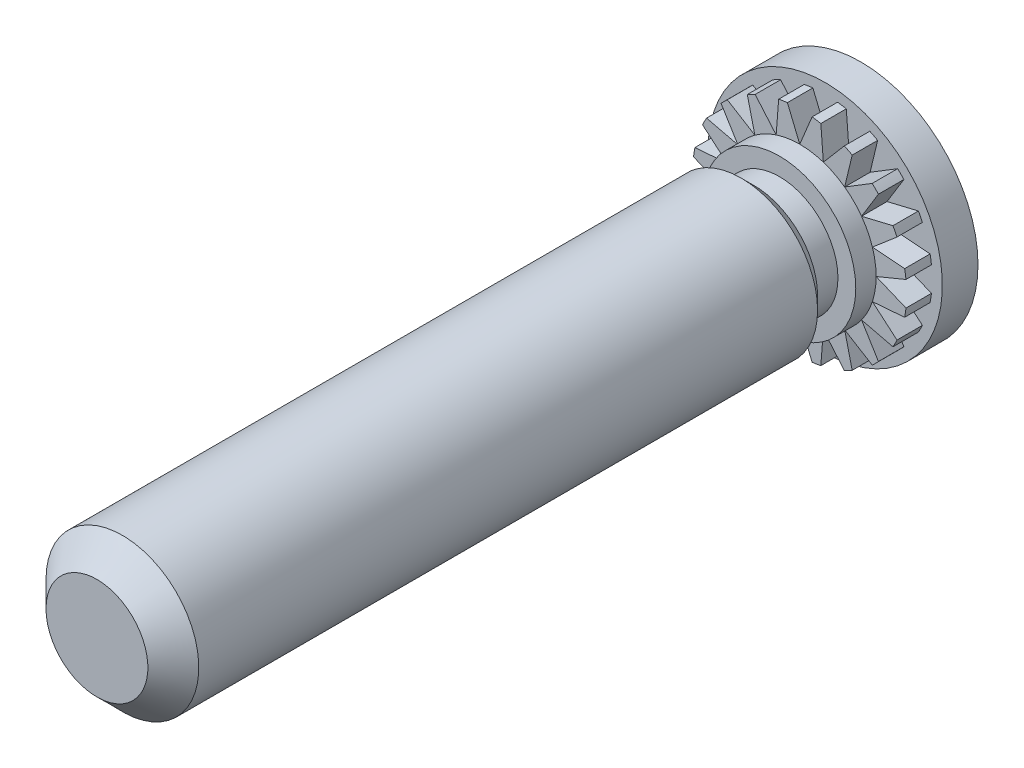
SolidWorks part; units mm, degrees
ref_plane "Спереди" through (0, 0, 0) normal (0, 0, 1) x (1, 0, 0)
ref_plane "Сверху" through (0, 0, 0) normal (0, 1, 0) x (1, 0, 0)
ref_plane "Справа" through (0, 0, 0) normal (1, 0, 0) x (0, 0, -1)
sketch "Эскиз1" plane through (0, 0, 0) normal (0, 0, 1) x (1, 0, 0)
  circle A0 centre (0, 0) radius 2.3
  dimension "D1" = 4.6
extrude "Вытянуть1" add sketch "Эскиз1" along normal blind 1.2
ref_axis "Ось1" through (0, 0, 10.6426) along (0, 0, -1)
sketch "Эскиз2" plane through (0, 0, 1.2) normal (0, 0, 1) x (1, 0, 0)
  circle A0 centre (0, 0) radius 1.5
  dimension "D1" = 3
extrude "Вытянуть2" add sketch "Эскиз2" along normal blind 1.5
sketch "Эскиз3" plane through (0, 0, 1.2) normal (0, 0, 1) x (1, 0, 0)
  line L0 (0, 0) -> (0, 2.3) construction
  line L1 (-0.3314, 2.3) -> (0.3314, 2.3)
  line L2 (0.3314, 2.3) -> (0, 1.5)
  line L3 (0, 1.5) -> (-0.3314, 2.3)
  circle A0 centre (0, 0) radius 2.3 construction
  circle A1 centre (0, 0) radius 1.5 construction
  dimension "D1" = 45
extrude "Вырез-Вытянуть1" cut sketch "Эскиз3" against normal blind 0.5
pattern_circular "Круговой массив1" count 20 over 360 about axis through (0, 0, 10.6426) along (0, 0, -1) of "Вырез-Вытянуть1"
sketch "Эскиз4" plane through (0, 0, 0) normal (0, 1, 0) x (1, 0, 0)
  line L0 (0, -1.85) -> (1.5, -1.85) construction
  line L1 (0, -4.6295) -> (0, 2.1879) construction
  line L2 (-1.5, -2.7) -> (1.5, -2.7) construction
  line L3 (1.5, -1.6) -> (1.15, -1.6)
  line L4 (1.5, -1.6) -> (1.5, -2.1)
  line L5 (1.5, -2.1) -> (1.15, -2.1)
  line L6 (1.15, -1.6) -> (1.15, -2.1)
  dimension "D1" = 0.5
  dimension "D2" = 0.6
  dimension "D3" = 1.5
  dimension "D4" = 0.35
revolve "Вырез-Повернуть1" cut sketch "Эскиз4" angle 360 about axis through (0, 0, 10.6426) along (0, 0, -1)
sketch "Эскиз6" plane through (0, 0, 0) normal (1, 0, 0) x (0, 0, -1)
  line L0 (-2.7, 0) -> (-15, 0)
  line L1 (-2.7, 1.5) -> (-2.7, -1.5) construction
  line L2 (-10.6426, 0) -> (0.6656, 0) construction
  line L3 (-15, 0) -> (-15, -1.5)
  line L4 (-15, -1.5) -> (-2.7, -1.5)
  line L5 (-2.7, -1.5) -> (-2.7, 0)
  line L6 (0, -2.3) -> (0, 2.3) construction
  dimension "D1" = 15
  dimension "D2" = 1.5
revolve "Повернуть1" add sketch "Эскиз6" angle 360 about L0
chamfer "Фаска2" distance 0.5 angle 45 1 edges at (-1.5, 0, 15)
sketch "Эскиз7" plane through (0, 0, 1.2) normal (0, 0, 1) x (1, 0, 0)
  circle A0 centre (0, 0) radius 2.1
  circle A1 centre (0, 0) radius 2.3
  arc A2 (-1.0781, 2.0317) -> (-1.5991, 1.6532) centre (0, 0) ccw construction
  dimension "D1" = 0.2
extrude "Вырез-Вытянуть2" cut sketch "Эскиз7" against normal up to surface (0.5 mm away) up to face at (-1.9266, 0.626, 0.7)
chamfer "Фаска3" distance 0.25 angle 45 1 edges at (1.5, 0, 2.1)
